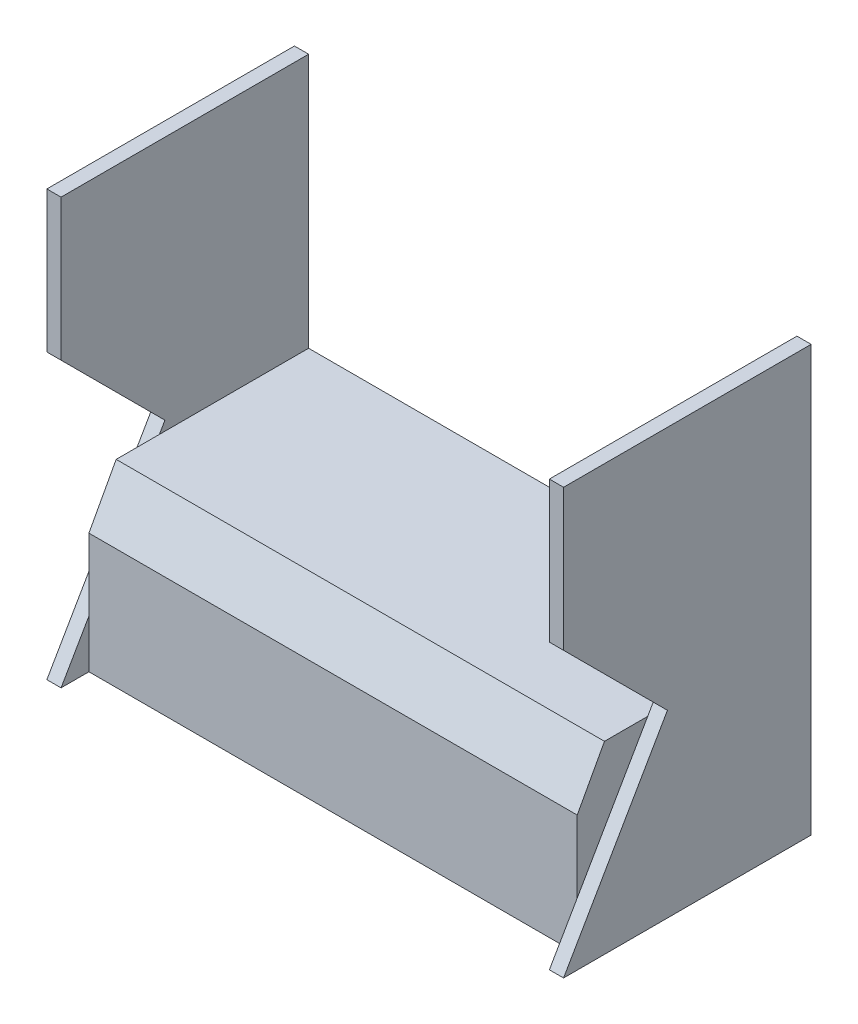
SolidWorks part; units mm, degrees
ref_plane "前视基准面" through (0, 0, 0) normal (0, 0, 1) x (1, 0, 0)
ref_plane "上视基准面" through (0, 0, 0) normal (0, 1, 0) x (1, 0, 0)
ref_plane "右视基准面" through (0, 0, 0) normal (1, 0, 0) x (0, 0, -1)
sketch "草图1" plane through (0, 0, 0) normal (1, 0, 0) x (0, 0, -1)
  line L1 (0, 0) -> (365.8487, 633.6686)
  line L2 (365.8487, 633.6686) -> (0, 999.5174)
  line L3 (0, 999.5174) -> (0, 1497)
  line L4 (0, 1497) -> (1722, 1497)
  line L5 (1722, 1497) -> (1722, 0)
  line L6 (1722, 0) -> (0, 0)
  dimension "D1" = 60
  dimension "D2" = 135
  dimension "D3" = 1722
  dimension "D4" = 1497
  dimension "D5" = 497.4826
extrude "凸台-拉伸1" add sketch "草图1" along normal blind 50
sketch "草图2" plane through (50, 0, 0) normal (1, 0, 0) x (0, 0, -1)
  line L0 (1722, 600) -> (194.0684, 600)
  line L1 (194.0684, 600) -> (98.1242, 423)
  line L2 (98.1242, 423) -> (98.1242, 0)
  line L3 (0, 0) -> (1722, 0) construction
  line L4 (98.1242, 0) -> (1722, 0)
  line L5 (1722, 0) -> (1722, 600)
  line L6 (1722, 0) -> (1722, 1497) construction
  dimension "D1" = 600
  dimension "D2" = 423
  dimension "D3" = 151.54
  dimension "D4" = 1527.9316
extrude "凸台-拉伸2" add sketch "草图2" along normal blind 1720
extrude "凸台-拉伸3" add sketch "草图1<2>" along normal blind 50 from surface starting at face at (1770, 324.6, -766.8634)
sketch "草图1<2>" plane through (0, 0, 0) normal (1, 0, 0) x (0, 0, -1) same geometry as "草图1"
sketch "草图3" plane through (0, 0, -1722) normal (0, 0, -1) x (-1, 0, 0)
  line L1 (0, 0) -> (-1820, 0)
  line L2 (0, 0) -> (0, 1497)
  line L3 (0, 1497) -> (-1820, 1497)
  line L4 (-1820, 0) -> (-1820, 1497)
extrude "切除-拉伸1" cut sketch "草图3" against normal blind 850
